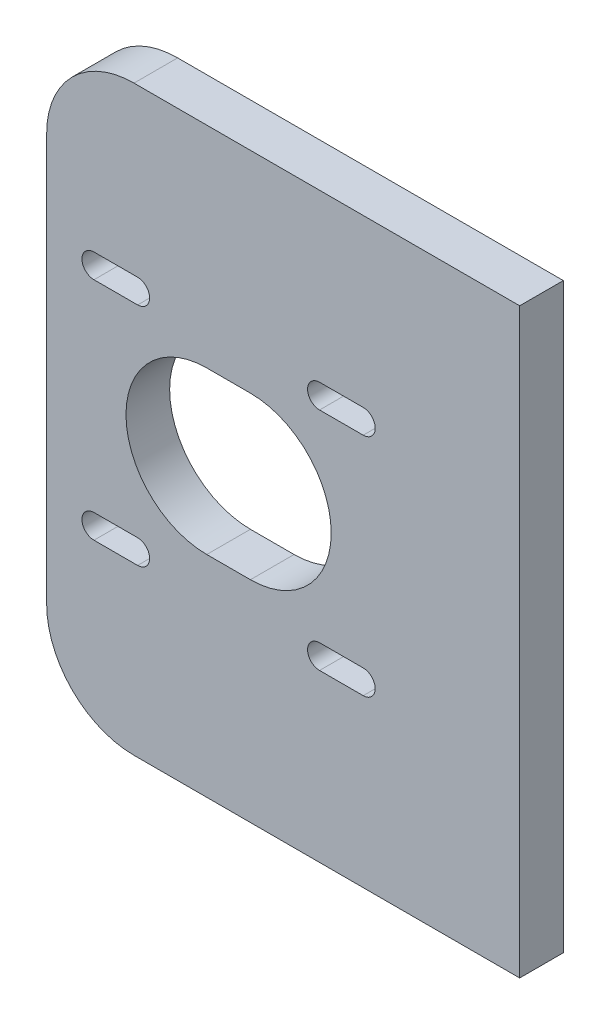
SolidWorks part; units mm, degrees
ref_plane "Alzado" through (0, 0, 0) normal (0, 0, 1) x (1, 0, 0)
ref_plane "Planta" through (0, 0, 0) normal (0, 1, 0) x (1, 0, 0)
ref_plane "Vista lateral" through (0, 0, 0) normal (1, 0, 0) x (0, 0, -1)
sketch "Croquis1" plane through (0, 0, 0) normal (0, 0, 1) x (1, 0, 0)
  line L1 (0, 0) -> (65, 0)
  line L2 (0, 0) -> (0, 80)
  line L3 (0, 80) -> (65, 80)
  line L4 (65, 0) -> (65, 80)
  dimension "D1" = 80
  dimension "D2" = 65
extrude "Saliente-Extruir1" add sketch "Croquis1" along normal blind 6
sketch "Croquis2" plane through (0, 0, 0) normal (0, 0, -1) x (-1, 0, 0)
  line L0 (0, 80) -> (0, 0) construction
  line L1 (0, 40) -> (-65, 40) construction
  line L4 (-65, 0) -> (-65, 80) construction
  line L7 (-22, 40) -> (-28, 40) construction
  line L10 (-22, 28.9) -> (-28, 28.9)
  line L19 (-22, 51.1) -> (-28, 51.1)
  line L20 (-6.5, 24.5) -> (-12.5, 24.5) construction
  line L21 (-6.5, 22.85) -> (-12.5, 22.85)
  line L22 (-6.5, 26.15) -> (-12.5, 26.15)
  line L23 (-37.5, 55.5) -> (-43.5, 55.5) construction
  line L24 (-37.5, 53.85) -> (-43.5, 53.85)
  line L25 (-37.5, 57.15) -> (-43.5, 57.15)
  line L26 (-37.5, 24.5) -> (-43.5, 24.5) construction
  line L27 (-37.5, 22.85) -> (-43.5, 22.85)
  line L28 (-37.5, 26.15) -> (-43.5, 26.15)
  line L29 (-6.5, 55.5) -> (-12.5, 55.5) construction
  line L30 (-6.5, 53.85) -> (-12.5, 53.85)
  line L31 (-6.5, 57.15) -> (-12.5, 57.15)
  arc A19 (-22, 28.9) -> (-22, 51.1) centre (-22, 40) ccw
  arc A20 (-28, 51.1) -> (-28, 28.9) centre (-28, 40) ccw
  arc A21 (-6.5, 22.85) -> (-6.5, 26.15) centre (-6.5, 24.5) ccw
  arc A22 (-12.5, 26.15) -> (-12.5, 22.85) centre (-12.5, 24.5) ccw
  arc A23 (-37.5, 53.85) -> (-37.5, 57.15) centre (-37.5, 55.5) ccw
  arc A24 (-43.5, 57.15) -> (-43.5, 53.85) centre (-43.5, 55.5) ccw
  arc A25 (-37.5, 22.85) -> (-37.5, 26.15) centre (-37.5, 24.5) ccw
  arc A26 (-43.5, 26.15) -> (-43.5, 22.85) centre (-43.5, 24.5) ccw
  arc A27 (-6.5, 53.85) -> (-6.5, 57.15) centre (-6.5, 55.5) ccw
  arc A28 (-12.5, 57.15) -> (-12.5, 53.85) centre (-12.5, 55.5) ccw
  point P6 (-25, 40)
  point P19 (-9.5, 24.5)
  point P28 (-40.5, 55.5)
  point P35 (-40.5, 24.5)
  point P48 (-9.5, 55.5)
  dimension "D2" = 6
  dimension "D3" = 11.1
  dimension "D4" = 3.3
  dimension "D5" = 6
  dimension "D6" = 40
  dimension "D7" = 15.5
  dimension "D8" = 15.5
  dimension "D9" = 3.3
  dimension "D10" = 6
  dimension "D17" = 3.3
  dimension "D18" = 6
  dimension "D19" = 3.3
  dimension "D20" = 6
  dimension "D21" = 15.5
  dimension "D22" = 15.5
  dimension "D23" = 15.5
  dimension "D24" = 15.5
  dimension "D25" = 15.5
  dimension "D26" = 15.5
extrude "Cortar-Extruir1" cut sketch "Croquis2" against normal through all
fillet "Redondeo1" radius 12 2 edges at (0, 0, 3) (0, 80, 3)
